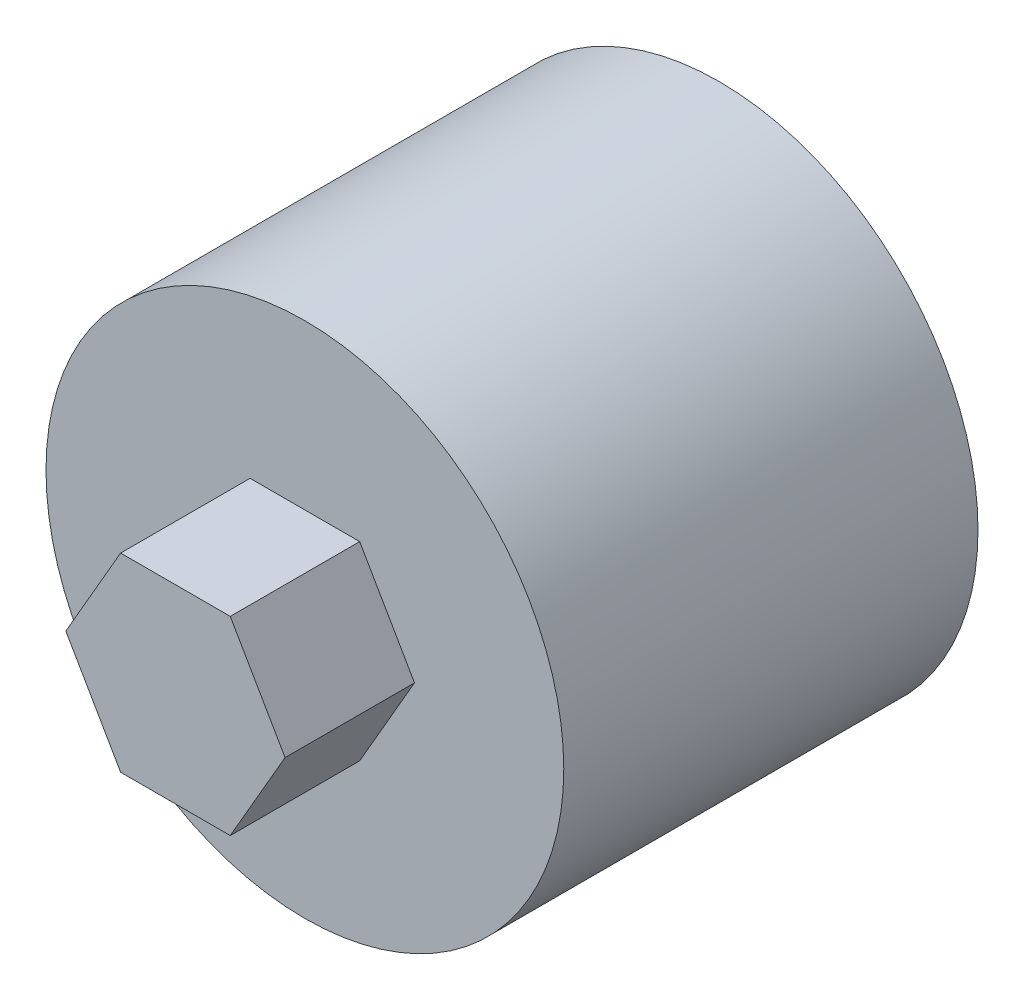
SolidWorks part; units mm, degrees
ref_plane "前视基准面" through (0, 0, 0) normal (0, 0, 1) x (1, 0, 0)
ref_plane "上视基准面" through (0, 0, 0) normal (0, 1, 0) x (1, 0, 0)
ref_plane "右视基准面" through (0, 0, 0) normal (1, 0, 0) x (0, 0, -1)
other "Configuration Table"
sketch "草图1" plane through (0, 0, 0) normal (0, 0, 1) x (1, 0, 0)
  line L0 (0, 0) -> (1.6914, 0.6156) construction
  line L1 (0, 0) -> (1.5832, 0.5954)
  line L2 (0, 0) -> (1.5832, -0.5954)
  line L3 (0, 0) -> (1.6914, -0.6156) construction
  line L4 (0, 0) -> (2.55, 0) construction
  line L5 (1.6914, 0.6156) -> (1.6914, -0.6156) construction
  circle A0 centre (0, 0) radius 1.65
  circle A1 centre (0, 0) radius 2.55
  circle A2 centre (0, 0) radius 1.6914 construction
  circle A3 centre (0, 0) radius 1.8 construction
  circle A4 centre (0, 0) radius 3
  spline S0 degree 4 poles (1.5832, 0.5954) (1.5953, 0.5999) (1.6299, 0.61) (1.6985, 0.6188) (1.8107, 0.6176) (1.9542, 0.5935) (2.1323, 0.5368) (2.3288, 0.4397) (2.527, 0.3033) (2.7182, 0.1281) (2.8863, -0.0692) (3.0309, -0.2841) (3.1583, -0.5243) (3.284, -0.8365) (3.3855, -1.2255) (3.4358, -1.6902) (3.4119, -2.2085) (3.3126, -2.7182) (3.1474, -3.2089) (2.918, -3.6756) (2.6387, -4.1089) (2.3029, -4.5102) (1.9385, -4.866) (1.5141, -5.1906) (1.1742, -5.4065) (0.7714, -5.6132) (0.5343, -5.7151) (0.2601, -5.8236) (0.1183, -5.8645) (-0.005, -5.9055) (-0.0434, -5.9147) (-0.0704, -5.9226) (-0.0848, -5.927) knots 0 0 0 0 0 0.005604 0.015718 0.02996 0.048734 0.068727 0.096889 0.125051 0.153212 0.181374 0.209535 0.237696 0.271429 0.327752 0.384075 0.440398 0.496721 0.553044 0.609367 0.66569 0.722013 0.778336 0.834659 0.890982 0.909091 0.954545 0.977273 0.988636 0.994318 1 1 1 1 1 construction
  spline S1 degree 4 poles (1.5832, 0.5954) (1.5953, 0.5999) (1.6299, 0.61) (1.6985, 0.6188) (1.8107, 0.6176) (1.9542, 0.5935) (2.1323, 0.5368) (2.3288, 0.4397) (2.527, 0.3033) (2.7182, 0.1281) (2.8863, -0.0692) (3.0309, -0.2841) (3.1583, -0.5243) (3.284, -0.8365) (3.3855, -1.2255) (3.4358, -1.6902) (3.4119, -2.2085) (3.3126, -2.7182) (3.1474, -3.2089) (2.918, -3.6756) (2.6387, -4.1089) (2.3029, -4.5102) (1.9385, -4.866) (1.5141, -5.1906) (1.1742, -5.4065) (0.8753, -5.5599) (0.734, -5.626) (0.6996, -5.6416) knots 0 0 0 0 0 0.005604 0.015718 0.02996 0.048734 0.068727 0.096889 0.125051 0.153212 0.181374 0.209535 0.237696 0.271429 0.327752 0.384075 0.440398 0.496721 0.553044 0.609367 0.66569 0.722013 0.778336 0.834659 0.890982 0.909091 0.909091 0.909091 0.909091 0.909091
  spline S2 degree 4 poles (1.5832, -0.5954) (1.5953, -0.5999) (1.6299, -0.61) (1.6985, -0.6188) (1.8107, -0.6176) (1.9542, -0.5935) (2.1323, -0.5368) (2.3288, -0.4397) (2.527, -0.3033) (2.7182, -0.1281) (2.8863, 0.0692) (3.0309, 0.2841) (3.1583, 0.5243) (3.284, 0.8365) (3.3855, 1.2255) (3.4358, 1.6902) (3.4119, 2.2085) (3.3126, 2.7182) (3.1474, 3.2089) (2.918, 3.6756) (2.6387, 4.1089) (2.3029, 4.5102) (1.9385, 4.866) (1.5141, 5.1906) (1.1742, 5.4065) (0.7714, 5.6132) (0.5343, 5.7151) (0.2601, 5.8236) (0.1183, 5.8645) (-0.005, 5.9055) (-0.0434, 5.9147) (-0.0704, 5.9226) (-0.0848, 5.927) knots 0 0 0 0 0 0.005604 0.015718 0.02996 0.048734 0.068727 0.096889 0.125051 0.153212 0.181374 0.209535 0.237696 0.271429 0.327752 0.384075 0.440398 0.496721 0.553044 0.609367 0.66569 0.722013 0.778336 0.834659 0.890982 0.909091 0.954545 0.977273 0.988636 0.994318 1 1 1 1 1 construction
  spline S3 degree 4 poles (1.5832, -0.5954) (1.5953, -0.5999) (1.6299, -0.61) (1.6985, -0.6188) (1.8107, -0.6176) (1.9542, -0.5935) (2.1323, -0.5368) (2.3288, -0.4397) (2.527, -0.3033) (2.7182, -0.1281) (2.8863, 0.0692) (3.0309, 0.2841) (3.1583, 0.5243) (3.284, 0.8365) (3.3855, 1.2255) (3.4358, 1.6902) (3.4119, 2.2085) (3.3126, 2.7182) (3.1474, 3.2089) (2.918, 3.6756) (2.6387, 4.1089) (2.3029, 4.5102) (1.9385, 4.866) (1.5141, 5.1906) (1.1742, 5.4065) (0.8753, 5.5599) (0.734, 5.626) (0.6996, 5.6416) knots 0 0 0 0 0 0.005604 0.015718 0.02996 0.048734 0.068727 0.096889 0.125051 0.153212 0.181374 0.209535 0.237696 0.271429 0.327752 0.384075 0.440398 0.496721 0.553044 0.609367 0.66569 0.722013 0.778336 0.834659 0.890982 0.909091 0.909091 0.909091 0.909091 0.909091
  point P16 (1.6914, 0)
  dimension "内啮合齿顶圆直径" = 3.3
  dimension "内啮合分度圆直径" = 3.6
  dimension "内啮合基圆直径" = 3.3829
  dimension "内啮合齿根圆直径" = 5.1
  dimension "外径" = 6
  dimension "渐开线镜像线夹角" = 20
extrude "凸台-拉伸1" add sketch "草图1" along normal blind 4 contours A4 | A0
extrude "切除-拉伸2" cut sketch "草图1<3>" along normal through all contours A0 S3 A1 S1 region at (2.0287, 0, 0)
sketch "草图1<3>" plane through (0, 0, 0) normal (0, 0, 1) x (1, 0, 0) same geometry as "草图1"
pattern_circular "阵列(圆周)1" count 9 over 360 about axis through (0, 0, 4) along (0, 0, 1) of "切除-拉伸2"
sketch "草图2" plane through (0, 0, 4) normal (0, 0, 1) x (1, 0, 0)
  line L1 (0.6351, 1.1) -> (-0.6351, 1.1)
  line L2 (-0.6351, 1.1) -> (-1.2702, 0)
  line L3 (-1.2702, 0) -> (-0.6351, -1.1)
  line L4 (-0.6351, -1.1) -> (0.6351, -1.1)
  line L5 (0.6351, -1.1) -> (1.2702, 0)
  line L6 (1.2702, 0) -> (0.6351, 1.1)
  circle A0 centre (0, 0) radius 3
  circle A1 centre (0, 0) radius 3 construction
  circle A2 centre (0, 0) radius 1.2702
  circle A3 centre (0, 0) radius 1.1 construction
  dimension "D1" = 2.2
extrude "凸台-拉伸2" add sketch "草图2" along normal blind 0.8 contours A0
extrude "凸台-拉伸3" add sketch "草图2<3>" along normal blind 1.5 from surface contours L1 L2 L3 L4 L5 L6 starting at face at (3, 0, 4.8)
sketch "草图2<3>" plane through (0, 0, 4) normal (0, 0, 1) x (1, 0, 0) same geometry as "草图2"
equation "\"m\"= 0.4'模数"
equation "\"z1\"= 6'外啮合齿轮数"
equation "\"a\"= 20度'压力角"
equation "\"z2\"= 9'内啮合齿轮数"
equation "\"hax\"= 1'齿顶高系数"
equation "\"cx\"= 0.25'顶隙系数"
equation "\"ha\"= \"hax\" * \"m\"'齿顶高"
equation "\"hf\"= ( \"hax\" + \"cx\" ) * \"m\"'齿根高"
equation "\"d1\"= \"m\" * \"z1\"'外啮合分度圆直径"
equation "\"da1\"= ( \"z1\" + 2 ) * \"m\"'外啮合齿顶圆直径"
equation "\"df1\"= \"d1\" - 2 * \"hf\"'外啮合齿根圆直径"
equation "\"db1\"= \"d1\" * cos ( \"a\" )'外啮合基圆直径"
equation "\"p\"= \"m\" * PI'齿距"
equation "\"d2\"= \"m\" * \"z2\"'内啮合分度圆直径"
equation "\"db2\"= \"d2\" * cos ( \"a\" )'内啮合基圆直径"
equation "\"da2\"= ( \"z2\" - 2 ) * \"m\"'内啮合齿顶圆直径"
equation "\"df2\"= \"d2\" + 2 * \"hf\"'内啮合齿根圆直径"
equation "\"内啮合齿顶圆直径@草图1\" = \"da2\" + 1 * \"hf\""
equation "\"内啮合齿根圆直径@草图1\" = \"df2\" + 1 * \"hf\""
equation "\"内啮合分度圆直径@草图1\"= \"d2\""
equation "\"内啮合基圆直径@草图1\"= \"db2\""
equation "\"渐开线镜像线夹角@草图1\" = 360度 / 4 / \"z2\" + 360度 / 4 / \"z2\""
equation "\"do\"= IIF ( \"edo\" >= ( \"df2\" + 1 ) , \"edo\" , ( \"df2\" + 1 ) )'外圈直径"
equation "\"h\"= 4'厚度"
equation "\"外径@草图1\"= \"do\""
equation "\"厚度@凸台-拉伸1\"= \"h\""
equation "\"内啮合齿轮数@阵列(圆周)1\"= \"z2\""
equation "\"edo\"= 6'期望的外圈直径"
